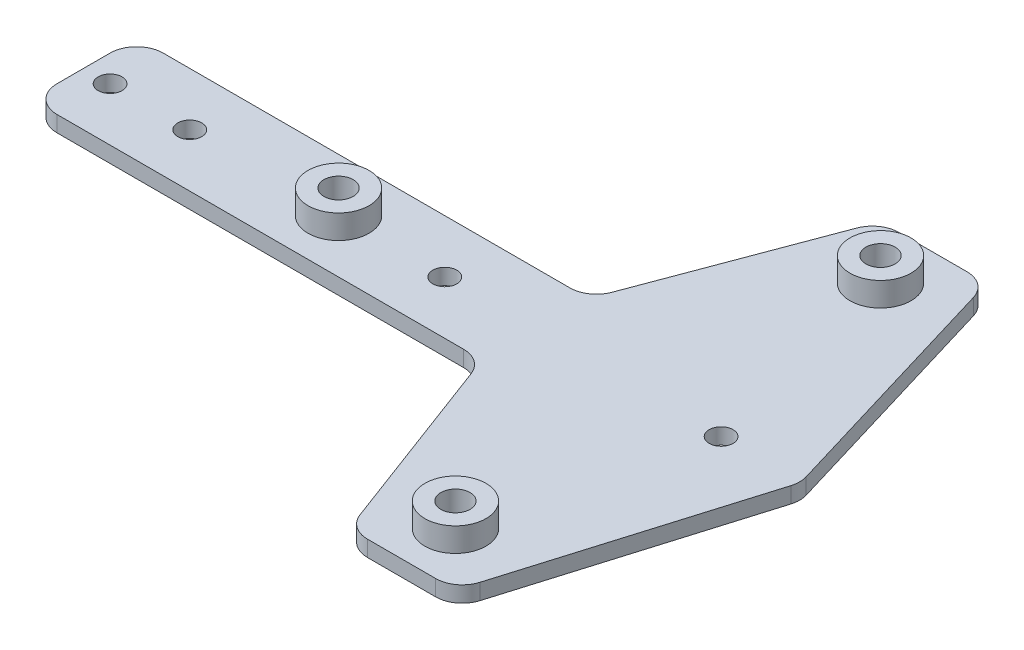
SolidWorks part; units mm, degrees
ref_plane "Front Plane" through (0, 0, 0) normal (0, 0, 1) x (1, 0, 0)
ref_plane "Top Plane" through (0, 0, 0) normal (0, 1, 0) x (1, 0, 0)
ref_plane "Right Plane" through (0, 0, 0) normal (1, 0, 0) x (0, 0, -1)
sketch "Sketch1" plane through (0, 0, 0) normal (0, 1, 0) x (1, 0, 0)
  line L0 (-55, 10) -> (6.535, 10)
  line L1 (11.2166, 13.2444) -> (23.7834, 46.7556)
  line L2 (28.465, 50) -> (41.2798, 50)
  line L3 (46.069, 46.4367) -> (59.569, 1.4367)
  line L4 (59.569, -1.4367) -> (46.069, -46.4367)
  line L5 (41.2798, -50) -> (28.465, -50)
  line L6 (23.7834, -46.7556) -> (11.2166, -13.2444)
  line L7 (6.535, -10) -> (-55, -10)
  line L8 (-60, -5) -> (-60, 5)
  line L9 (-60, 0) -> (60, 0) construction
  line L10 (10, -10) -> (10, 10) construction
  line L11 (25, 50) -> (25, -50) construction
  line L12 (45, -50) -> (45, 50) construction
  arc A0 (6.535, 10) -> (11.2166, 13.2444) centre (6.535, 15) ccw
  arc A1 (23.7834, 46.7556) -> (28.465, 50) centre (28.465, 45) cw
  arc A2 (41.2798, 50) -> (46.069, 46.4367) centre (41.2798, 45) cw
  arc A3 (59.569, 1.4367) -> (59.569, -1.4367) centre (54.7798, 0) cw
  arc A4 (46.069, -46.4367) -> (41.2798, -50) centre (41.2798, -45) cw
  arc A5 (28.465, -50) -> (23.7834, -46.7556) centre (28.465, -45) cw
  arc A6 (11.2166, -13.2444) -> (6.535, -10) centre (6.535, -15) ccw
  arc A7 (-55, -10) -> (-60, -5) centre (-55, -5) cw
  arc A8 (-55, 10) -> (-60, 5) centre (-55, 5) ccw
  point P10 (25, 0)
  point P36 (-60, -10)
  point P39 (-60, 10)
  dimension "D7" = 5
  dimension "D1" = 20
  dimension "D2" = 70
  dimension "D3" = 15
  dimension "D4" = 20
  dimension "D5" = 15
  dimension "D6" = 100
extrude "Boss-Extrude1" add sketch "Sketch1" along normal blind 3
sketch "Sketch2" plane through (0, 3, 0) normal (0, 1, 0) x (1, 0, 0)
  line L0 (-27, 0) -> (0, 0) construction
  line L1 (0, 0) -> (35, 0) construction
  line L2 (35, 40) -> (35, -40) construction
  circle A0 centre (-27, 0) radius 2.75
  circle A1 centre (35, 40) radius 2.75
  circle A2 centre (35, -40) radius 2.75
  arc A3 (59.569, -1.4367) -> (59.569, 1.4367) centre (54.7798, 0) ccw construction
  dimension "D4" = 5.5
  dimension "D1" = 62
  dimension "D2" = 19.7798
  dimension "D3" = 80
extrude "Cut-Extrude1" cut sketch "Sketch2" against normal through all
sketch "Sketch3" plane through (0, 3, 0) normal (0, 1, 0) x (1, 0, 0)
  circle A0 centre (35, -40) radius 2.75 construction
  circle A1 centre (-27, 0) radius 2.75 construction
  circle A2 centre (35, 40) radius 2.75 construction
  circle A3 centre (35, -40) radius 2.75
  circle A4 centre (-27, 0) radius 2.75
  circle A5 centre (35, 40) radius 2.75
  circle A6 centre (-27, 0) radius 5.75
  circle A7 centre (35, 40) radius 5.75
  circle A8 centre (35, -40) radius 5.75
  dimension "D1" = 3
extrude "Boss-Extrude2" add sketch "Sketch3" along normal blind 4.5
sketch "Sketch4" plane through (0, 3, 0) normal (0, 1, 0) x (1, 0, 0)
  line L0 (-55, 0) -> (0, 0) construction
  line L1 (0, 0) -> (45, 0) construction
  circle A0 centre (-55, 0) radius 2.25
  circle A1 centre (45, 0) radius 2.25
  circle A3 centre (-7, 0) radius 2.25
  arc A4 (59.569, -1.4367) -> (59.569, 1.4367) centre (54.7798, 0) ccw construction
  dimension "D2" = 4.5
  dimension "D3" = 9.7798
  dimension "D1" = 52
  dimension "D4" = 100
extrude "Cut-Extrude2" cut sketch "Sketch4" against normal through all
sketch "Sketch5" plane through (0, 0, 0) normal (0, 1, 0) x (1, 0, 0)
  line L1 (-55, 10) -> (-70, 10)
  line L2 (-55, 10) -> (-55, -10)
  line L3 (-55, -10) -> (-70, -10)
  line L4 (-75, 5) -> (-75, -5)
  line L5 (-55, -10) -> (6.535, -10) construction
  line L6 (-60, 5) -> (-60, -5) construction
  line L7 (-70, 0) -> (-55, 0) construction
  arc A0 (-70, 10) -> (-75, 5) centre (-70, 5) ccw
  arc A1 (-70, -10) -> (-75, -5) centre (-70, -5) cw
  circle A2 centre (-70, 0) radius 2.25
  circle A3 centre (-55, 0) radius 2.25 construction
  point P18 (-66.0431, 0)
  dimension "D2" = 5
  dimension "D1" = 15
  dimension "D3" = 15
extrude "Boss-Extrude3" add sketch "Sketch5" along normal blind 3
sketch "Sketch6" plane through (0, 3, 0) normal (0, 1, 0) x (1, 0, 0)
  line L0 (-55, -2.25) -> (-55, 2.25) construction
  circle A0 centre (-55, 0) radius 2.25
  arc A1 (-55, -2.25) -> (-55, 2.25) centre (-55, 0) ccw construction
extrude "Cut-Extrude3" cut sketch "Sketch6" against normal through all
